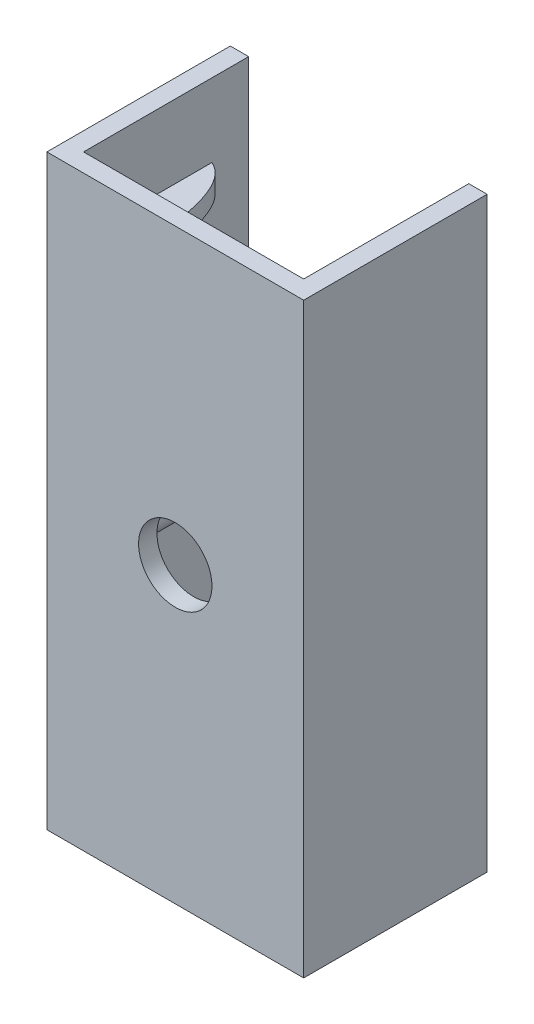
SolidWorks part; units mm, degrees
ref_plane "Alzado" through (0, 0, 0) normal (0, 0, 1) x (1, 0, 0)
ref_plane "Planta" through (0, 0, 0) normal (0, 1, 0) x (1, 0, 0)
ref_plane "Vista lateral" through (0, 0, 0) normal (1, 0, 0) x (0, 0, -1)
sketch "Croquis1" plane through (0, 0, 0) normal (0, 0, 1) x (1, 0, 0)
  line L0 (117743.4169, 152337.8366) -> (131743.4169, 152337.8366)
  line L1 (131743.4169, 152337.8366) -> (131743.4169, 161337.8366)
  line L2 (131743.4169, 161337.8366) -> (140743.4169, 161337.8366)
  line L3 (140743.4169, 161337.8366) -> (140743.4169, 175337.8366)
  line L4 (140743.4169, 175337.8366) -> (117743.4169, 175337.8366)
  line L5 (117743.4169, 175337.8366) -> (117743.4169, 152337.8366)
  line L6 (118743.4169, 152337.8366) -> (118743.4169, 166437.8366)
  line L7 (118743.4169, 174337.8366) -> (122843.4169, 174337.8366)
  line L8 (130743.4169, 152337.8366) -> (130743.4169, 162337.8366)
  line L9 (140743.4169, 162337.8366) -> (130743.4169, 162337.8366)
  line L10 (131743.4169, 161337.8366) -> (108743.4169, 161337.8366)
  line L11 (108743.4169, 161337.8366) -> (108743.4169, 162337.8366)
  line L12 (108743.4169, 162337.8366) -> (122843.4169, 162337.8366)
  line L13 (131743.4169, 161337.8366) -> (131743.4169, 184337.8366)
  line L14 (131743.4169, 184337.8366) -> (130743.4169, 184337.8366)
  line L15 (130743.4169, 184337.8366) -> (130743.4169, 170237.8366)
  line L16 (118743.4169, 174337.8366) -> (118743.4169, 184337.8366)
  line L17 (118743.4169, 184337.8366) -> (117743.4169, 184337.8366)
  line L18 (117743.4169, 184337.8366) -> (117743.4169, 175337.8366)
  line L19 (118743.4169, 174337.8366) -> (108743.4169, 174337.8366)
  line L20 (108743.4169, 174337.8366) -> (108743.4169, 175337.8366)
  line L21 (108743.4169, 175337.8366) -> (117743.4169, 175337.8366)
  line L22 (108743.4169, 174337.8366) -> (108743.4169, 162337.8366)
  line L23 (118743.4169, 184337.8366) -> (130743.4169, 184337.8366)
  line L24 (122743.4169, 174237.8366) -> (122743.4169, 172837.8366)
  line L25 (124243.4169, 171337.8366) -> (125243.4169, 171337.8366)
  line L26 (126743.4169, 172837.8366) -> (126743.4169, 174237.8366)
  line L27 (118843.4169, 170337.8366) -> (120243.4169, 170337.8366)
  line L28 (121743.4169, 168837.8366) -> (121743.4169, 167837.8366)
  line L29 (120243.4169, 166337.8366) -> (118843.4169, 166337.8366)
  line L30 (130643.4169, 170337.8366) -> (129243.4169, 170337.8366)
  line L31 (127743.4169, 168837.8366) -> (127743.4169, 167837.8366)
  line L32 (129243.4169, 166337.8366) -> (130643.4169, 166337.8366)
  line L33 (122743.4169, 162437.8366) -> (122743.4169, 163837.8366)
  line L34 (124243.4169, 165337.8366) -> (125243.4169, 165337.8366)
  line L35 (126743.4169, 163837.8366) -> (126743.4169, 162337.8366)
  line L36 (121743.4169, 168337.8366) -> (127743.4169, 168337.8366) construction
  line L37 (118743.4169, 170237.8366) -> (120243.4169, 170237.8366)
  line L38 (118843.4169, 174237.8366) -> (122743.4169, 174237.8366)
  line L39 (121643.4169, 168837.8366) -> (121643.4169, 167837.8366)
  line L40 (118843.4169, 162437.8366) -> (118843.4169, 166337.8366)
  line L41 (118843.4169, 162437.8366) -> (122743.4169, 162437.8366)
  line L42 (130643.4169, 174237.8366) -> (130643.4169, 170337.8366)
  line L43 (120243.4169, 166437.8366) -> (118743.4169, 166437.8366)
  line L44 (118743.4169, 174237.8366) -> (140743.4169, 174237.8366) construction
  line L45 (122843.4169, 162337.8366) -> (122843.4169, 163837.8366)
  line L46 (124243.4169, 165237.8366) -> (125243.4169, 165237.8366)
  line L47 (126643.4169, 163837.8366) -> (126643.4169, 162337.8366)
  line L48 (130743.4169, 170237.8366) -> (129243.4169, 170237.8366)
  line L49 (127843.4169, 168837.8366) -> (127843.4169, 167837.8366)
  line L50 (129243.4169, 166437.8366) -> (130743.4169, 166437.8366)
  line L51 (122843.4169, 174337.8366) -> (122843.4169, 172837.8366)
  line L52 (124243.4169, 171437.8366) -> (125243.4169, 171437.8366)
  line L53 (126643.4169, 172837.8366) -> (126643.4169, 174337.8366)
  line L54 (130643.4169, 166337.8366) -> (130643.4169, 162437.8366)
  line L55 (130743.4169, 166437.8366) -> (130743.4169, 162337.8366)
  line L56 (129243.4169, 166337.8366) -> (130743.4169, 166337.8366) construction
  line L57 (130743.4169, 170337.8366) -> (129243.4169, 170337.8366) construction
  line L58 (126643.4169, 174337.8366) -> (140743.4169, 174337.8366)
  line L59 (118743.4169, 174337.8366) -> (140743.4169, 174337.8366) construction
  line L60 (126743.4169, 174237.8366) -> (130643.4169, 174237.8366)
  line L61 (126743.4169, 172837.8366) -> (126743.4169, 174337.8366) construction
  line L62 (122743.4169, 174337.8366) -> (122743.4169, 172837.8366) construction
  line L63 (118743.4169, 170237.8366) -> (118743.4169, 174337.8366)
  line L64 (118843.4169, 170337.8366) -> (118843.4169, 174237.8366)
  line L65 (118743.4169, 170337.8366) -> (120243.4169, 170337.8366) construction
  line L66 (120243.4169, 166337.8366) -> (118743.4169, 166337.8366) construction
  line L67 (126743.4169, 162437.8366) -> (130643.4169, 162437.8366)
  line L68 (122743.4169, 162337.8366) -> (122743.4169, 163837.8366) construction
  line L69 (126643.4169, 162337.8366) -> (130743.4169, 162337.8366)
  arc A0 (125243.4169, 165337.8366) -> (126743.4169, 163837.8366) centre (125243.4169, 163837.8366) cw
  arc A1 (122743.4169, 163837.8366) -> (124243.4169, 165337.8366) centre (124243.4169, 163837.8366) cw
  arc A2 (127743.4169, 167837.8366) -> (129243.4169, 166337.8366) centre (129243.4169, 167837.8366) ccw
  arc A3 (129243.4169, 170337.8366) -> (127743.4169, 168837.8366) centre (129243.4169, 168837.8366) ccw
  arc A4 (125243.4169, 171337.8366) -> (126743.4169, 172837.8366) centre (125243.4169, 172837.8366) ccw
  arc A5 (122743.4169, 172837.8366) -> (124243.4169, 171337.8366) centre (124243.4169, 172837.8366) ccw
  arc A6 (120243.4169, 170337.8366) -> (121743.4169, 168837.8366) centre (120243.4169, 168837.8366) cw
  arc A7 (121743.4169, 167837.8366) -> (120243.4169, 166337.8366) centre (120243.4169, 167837.8366) cw
  circle A8 centre (124743.4169, 168337.8366) radius 2000
  arc A9 (120243.4169, 170237.8366) -> (121643.4169, 168837.8366) centre (120243.4169, 168837.8366) cw
  arc A10 (121643.4169, 167837.8366) -> (120243.4169, 166437.8366) centre (120243.4169, 167837.8366) cw
  arc A11 (122843.4169, 163837.8366) -> (124243.4169, 165237.8366) centre (124243.4169, 163837.8366) cw
  arc A12 (125243.4169, 165237.8366) -> (126643.4169, 163837.8366) centre (125243.4169, 163837.8366) cw
  arc A13 (129243.4169, 170237.8366) -> (127843.4169, 168837.8366) centre (129243.4169, 168837.8366) ccw
  arc A14 (127843.4169, 167837.8366) -> (129243.4169, 166437.8366) centre (129243.4169, 167837.8366) ccw
  arc A15 (122843.4169, 172837.8366) -> (124243.4169, 171437.8366) centre (124243.4169, 172837.8366) ccw
  arc A16 (125243.4169, 171437.8366) -> (126643.4169, 172837.8366) centre (125243.4169, 172837.8366) ccw
  circle A17 centre (124743.4169, 168337.8366) radius 1900
  point P34 (126743.4169, 163087.8366)
  point P39 (126743.4169, 165337.8366)
  point P42 (122743.4169, 165337.8366)
  point P45 (127743.4169, 166337.8366)
  point P48 (127743.4169, 170337.8366)
  point P51 (126743.4169, 171337.8366)
  point P54 (122743.4169, 171337.8366)
  point P57 (121743.4169, 170337.8366)
  point P60 (121743.4169, 166337.8366)
  point P105 (0, 0)
  dimension "D21" = 1500
  dimension "D22" = 4000
  dimension "D1" = 12000
  dimension "D2" = 1000
  dimension "D3" = 1000
  dimension "D4" = 1000
  dimension "D5" = 1000
  dimension "D6" = 12000
  dimension "D7" = 9000
  dimension "D8" = 9000
  dimension "D9" = 9000
  dimension "D10" = 9000
  dimension "D11" = 4000
  dimension "D12" = 4000
  dimension "D13" = 4000
  dimension "D14" = 4000
  dimension "D18" = 4000
  dimension "D19" = 4000
  dimension "D20" = 3000
  dimension "D23" = 100
  dimension "D24" = 100
  dimension "D25" = 100
  dimension "D26" = 100
ref_plane "Plano1" through (0, 161337.8366, 0) normal (0, 1, 0) x (1, 0, 0)
ref_plane "Plano2" through (0, 175337.8366, 0) normal (0, 1, 0) x (1, 0, 0)
ref_plane "Plano3" through (117743.4169, 0, 0) normal (1, 0, 0) x (0, 0, -1)
ref_plane "Plano4" through (131743.4169, 0, 0) normal (1, 0, 0) x (0, 0, -1)
ref_plane "Plano5" through (113243.4169, 0, 0) normal (1, 0, 0) x (0, 0, -1)
ref_plane "Plano6" through (0, 179837.8366, 0) normal (0, 1, 0) x (1, 0, 0)
ref_plane "Plano7" through (136243.4169, 0, 0) normal (1, 0, 0) x (0, 0, -1)
ref_plane "Plano8" through (0, 156837.8366, 0) normal (0, 1, 0) x (1, 0, 0)
sketch "Croquis2" plane through (0, 156837.8366, 0) normal (0, 1, 0) x (1, 0, 0)
  line L0 (117743.4169, 0) -> (131743.4169, 0) construction
  line L1 (117743.4169, 0) -> (131743.4169, 0)
  line L2 (131743.4169, 0) -> (131743.4169, 8000)
  line L3 (131743.4169, 8000) -> (130743.4169, 8000)
  line L4 (130743.4169, 8000) -> (130743.4169, 1000)
  line L5 (130743.4169, 1000) -> (118743.4169, 1000)
  line L6 (118743.4169, 1000) -> (118743.4169, 8000)
  line L7 (118743.4169, 8000) -> (117743.4169, 8000)
  line L8 (117743.4169, 8000) -> (117743.4169, 0)
  spline S0 degree 2 poles (130743.4169, 8000) (128761.6752, 7234.3483) (128743.4169, 1000) knots 0 0 0 0.590989 0.590989 0.590989
  spline S1 degree 2 poles (118743.4169, 8000) (120739.8111, 7120.5788) (120743.4169, 1000) knots 0 0 0 0.514461 0.514461 0.514461
  point P10 (0, 0)
  dimension "D1" = 1000
  dimension "D2" = 1000
  dimension "D3" = 1000
  dimension "D4" = 7000
  dimension "D5" = 7000
  dimension "D6" = 2000
  dimension "D7" = 2000
sketch "Croquis3" plane through (0, 179837.8366, 0) normal (0, 1, 0) x (1, 0, 0)
  line L0 (118743.4169, 1000) -> (118743.4169, 8000) construction
  line L1 (130743.4169, 1000) -> (118743.4169, 1000) construction
  line L2 (130743.4169, 8000) -> (130743.4169, 1000) construction
  line L3 (118743.4169, 1000) -> (118743.4169, 8000)
  line L4 (130743.4169, 1000) -> (118743.4169, 1000)
  line L5 (130743.4169, 8000) -> (130743.4169, 1000)
  parabola Q0 (118743.4169, 8000) -> (120743.4169, 1000) focus (118361.6774, 7241.9739) apex (118662.5082, 8033.1777) construction
  parabola Q1 (130743.4169, 8000) -> (128743.4169, 1000) focus (131040.6578, 7282.3326) apex (130778.3168, 8013.005) construction
  parabola Q2 (118743.4169, 8000) -> (120743.4169, 1000) focus (118361.6774, 7241.9739) apex (118662.5082, 8033.1777)
  parabola Q3 (130743.4169, 8000) -> (128743.4169, 1000) focus (131040.6578, 7282.3326) apex (130778.3168, 8013.005)
sketch "Croquis4" plane through (113243.4169, 0, 0) normal (1, 0, 0) x (0, 0, -1)
  line L0 (0, 174337.8366) -> (0, 162337.8366) construction
  line L1 (0, 174337.8366) -> (0, 162337.8366)
  line L2 (0, 162337.8366) -> (8000, 162337.8366)
  line L3 (0, 174337.8366) -> (8000, 174337.8366)
  spline S0 degree 2 poles (8000, 162337.8366) (6698.659, 164240.8241) (0, 164337.8366) knots 0 0 0 0.70753 0.70753 0.70753
  spline S1 degree 2 poles (8000, 174337.8366) (6599.8546, 172118.7435) (0, 172337.8366) knots 0 0 0 0.648378 0.648378 0.648378
  dimension "D1" = 8000
  dimension "D2" = 2000
  dimension "D3" = 2000
sketch "Croquis5" plane through (136243.4169, 0, 0) normal (1, 0, 0) x (0, 0, -1)
  line L0 (0, 162337.8366) -> (8000, 162337.8366) construction
  line L1 (0, 174337.8366) -> (0, 162337.8366) construction
  line L2 (0, 174337.8366) -> (8000, 174337.8366) construction
  line L3 (0, 162337.8366) -> (8000, 162337.8366)
  line L4 (0, 174337.8366) -> (0, 162337.8366)
  line L5 (0, 174337.8366) -> (8000, 174337.8366)
  parabola Q0 (8000, 162337.8366) -> (0, 164337.8366) focus (7402.6379, 161620.0634) apex (8222.0253, 161894.2353) construction
  parabola Q1 (8000, 174337.8366) -> (0, 172337.8366) focus (7073.338, 175098.4045) apex (8142.0414, 174597.2807) construction
  parabola Q2 (8000, 162337.8366) -> (0, 164337.8366) focus (7402.6379, 161620.0634) apex (8222.0253, 161894.2353)
  parabola Q3 (8000, 174337.8366) -> (0, 172337.8366) focus (7073.338, 175098.4045) apex (8142.0414, 174597.2807)
extrude "Saliente-Extruir1" add sketch "Croquis1" against normal blind 1000 contours L15 L58 L13 L4 | L14 L15 L4 L13 | L23 L16 L4 L15 | L17 L18 L4 L16 | L19 L16 L4 L5 | L12 L5 L10 L6 | L6 L10 L5 L0 | L8 L10 L6 L0 | L1 L10 L8 L0 | L10 L13 L9 L8 | A12 L46 A11 L45 L12 L6 L10 L8 L69 L47 | L49 A14 L50 L55 L9 L13 L58 L15 L48 A13 | L52 A16 L53 L58 L15 L4 L16 L7 L51 A15 | A10 L39 A9 L37 L63 L19 L5 L12 L6 L43 | L28 A7 L29 L40 L41 L33 A1 L34 A0 L35 L67 L54 L32 A2 L31 A3 L30 L42 L60 L26 A4 L25 A5 L24 L38 L64 L27 A6 A8 | A16 L52 A15 L51 L7 L63 L37 A9 L39 A10 L43 L6 L12 L45 A11 L46 A12 L47 L69 L35 A0 L34 A1 L33 L41 L40 L29 A7 L28 A6 L27 L64 L38 L24 A5 L25 A4 L26 L60 L42 L30 A3 L31 A2 L32 L54 L67 L55 region at (118243.4169, 156837.8366, 0) region at (124743.4169, 156837.8366, 0) region at (118243.4169, 161837.8366, 0) region at (131243.4169, 156837.8366, 0) region at (124743.4169, 162689.636, 0) region at (119095.2163, 168337.8366, 0) region at (131243.4169, 161837.8366, 0) region at (126910.2941, 163137.8366, 0) region at (118760.3875, 164387.8366, 0) region at (118243.4169, 174837.8366, 0) region at (130391.6175, 168337.8366, 0) region at (118243.4169, 179837.8366, 0) region at (124743.4169, 173986.0372, 0) region at (124743.4169, 179837.8366, 0) region at (131243.4169, 174837.8366, 0) region at (131243.4169, 179837.8366, 0)
extrude "Saliente-Extruir2" add sketch "Croquis1<6>" against normal blind 10000 contours L15 L58 L13 L4 | L14 L15 L4 L13 | L17 L18 L4 L16 | L19 L16 L4 L5 | L12 L5 L10 L6 | L6 L10 L5 L0 | L1 L10 L8 L0 | L10 L13 L9 L8 | L49 A14 L50 L55 L9 L13 L58 L15 L48 A13 | A10 L39 A9 L37 L63 L19 L5 L12 L6 L43 region at (118243.4169, 156837.8366, 0) region at (118243.4169, 161837.8366, 0) region at (131243.4169, 156837.8366, 0) region at (119095.2163, 168337.8366, 0) region at (131243.4169, 161837.8366, 0) region at (118243.4169, 174837.8366, 0) region at (130391.6175, 168337.8366, 0) region at (118243.4169, 179837.8366, 0) region at (131243.4169, 174837.8366, 0) region at (131243.4169, 179837.8366, 0)
sketch "Croquis1<6>" plane through (0, 0, 0) normal (0, 0, 1) x (1, 0, 0) same geometry as "Croquis1"
extrude "Saliente-Extruir3" add sketch "Croquis2" along normal blind 500 and the other way blind 500 contours L4 S0 L5 | S1 L6 L5 region at (119605.9639, 156837.8366, -3955.1574) region at (129880.6924, 156837.8366, -3967.5864)
extrude "Saliente-Extruir4" add sketch "Croquis3" along normal blind 500 and the other way blind 500 contours Q2 L3 L4 | L5 Q3 L4 region at (129880.6924, 179837.8366, -3967.5864) region at (119605.9639, 179837.8366, -3955.1574)
